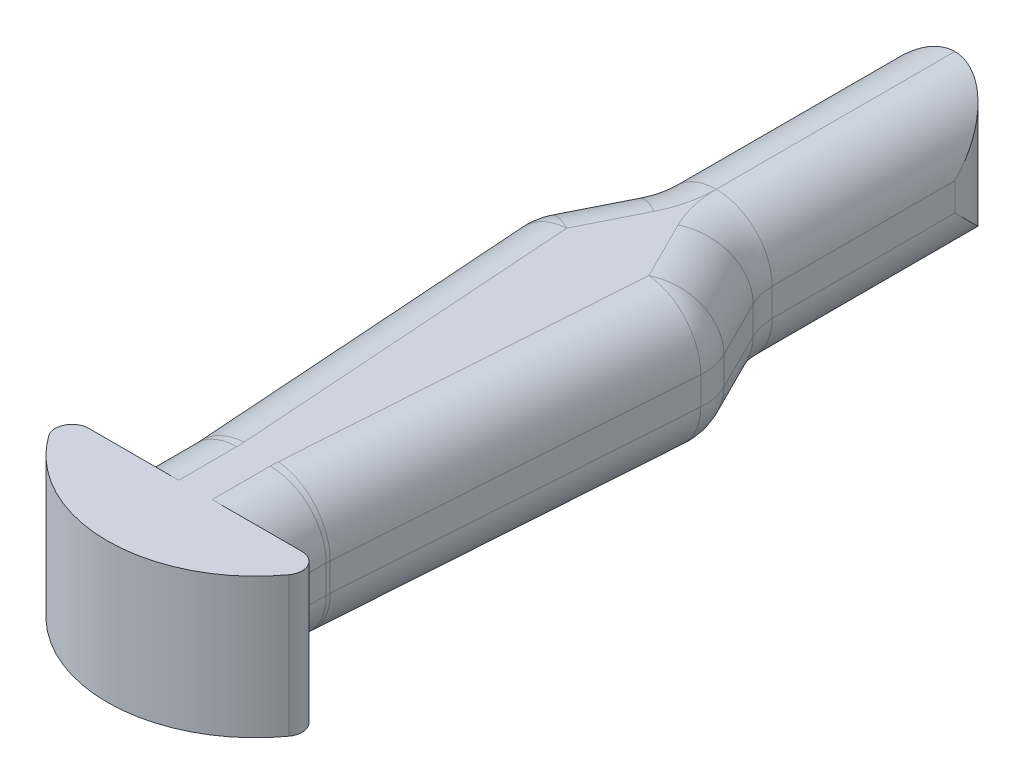
SolidWorks part; units mm, degrees
material "ABS"
ref_plane "Front Plane" through (0, 0, 0) normal (0, 0, 1) x (1, 0, 0)
ref_plane "Top Plane" through (0, 0, 0) normal (0, 1, 0) x (1, 0, 0)
ref_plane "Right Plane" through (0, 0, 0) normal (1, 0, 0) x (0, 0, -1)
sketch "草图1" plane through (0, 0, 0) normal (0, 1, 0) x (1, 0, 0)
  line L0 (0, 62.5) -> (0, -62.5)
  line L1 (-30, 62.5) -> (30, 62.5)
  line L2 (-30, 62.5) -> (-30, -62.5)
  line L3 (-30, -62.5) -> (30, -62.5)
  line L4 (30, 62.5) -> (30, -62.5)
  line L5 (-30, 62.5) -> (30, -62.5) construction
  line L6 (-30, -62.5) -> (30, 62.5) construction
  line L7 (-17.5, 2.5) -> (-10, 17.5)
  line L8 (0, -62.5) -> (13, -62.5)
  line L9 (0, -62.5) -> (0, 2.5)
  line L10 (0, 2.5) -> (13, 2.5)
  line L11 (13, -62.5) -> (13, 2.5)
  line L12 (0, -62.5) -> (-13, -62.5)
  line L13 (0, -62.5) -> (0, 2.5)
  line L14 (0, 2.5) -> (-13, 2.5)
  line L15 (-13, -62.5) -> (-13, 2.5)
  line L16 (30, 62.5) -> (10, 62.5)
  line L17 (30, 62.5) -> (30, 17.5)
  line L18 (30, 17.5) -> (10, 17.5)
  line L19 (10, 62.5) -> (10, 17.5)
  line L20 (-30, 62.5) -> (-10, 62.5)
  line L21 (-30, 62.5) -> (-30, 17.5)
  line L22 (-30, 17.5) -> (-10, 17.5)
  line L23 (-10, 62.5) -> (-10, 17.5)
  line L24 (0, -62.5) -> (17.5, -62.5)
  line L25 (0, -62.5) -> (0, 2.5)
  line L26 (0, 2.5) -> (17.5, 2.5)
  line L27 (17.5, -62.5) -> (17.5, 2.5)
  line L28 (0, -62.5) -> (-17.5, -62.5)
  line L29 (0, -62.5) -> (0, 2.5)
  line L30 (0, 2.5) -> (-17.5, 2.5)
  line L31 (-17.5, -62.5) -> (-17.5, 2.5)
  line L32 (10, 17.5) -> (17.5, 2.5)
  line L33 (-17.5, 2.5) -> (-13, -62.5)
  line L34 (17.5, 2.5) -> (13, -62.5)
  line L35 (-13, -62.5) -> (-13, -85.2565)
  line L36 (-13, -62.5) -> (13, -62.5)
  line L37 (-13, -62.5) -> (-13, -72.5)
  line L38 (-13, -72.5) -> (13, -72.5)
  line L39 (13, -62.5) -> (13, -72.5)
  line L40 (-13, -85.2565) -> (13, -85.2565)
  line L41 (13, -85.2565) -> (13, -62.5)
  line L42 (-13, -73.2227) -> (-24.2111, -73.2227)
  line L43 (-24.2111, -73.2227) -> (24.2111, -73.2227)
  arc A0 (-13, -73.2227) -> (13, -73.2227) centre (0, -62.5) ccw
  arc A1 (16.8516, -62.5) -> (-16.8516, -62.5) centre (0, -62.5) ccw
  arc A2 (26.4793, -62.5) -> (-26.4793, -62.5) centre (0, -62.5) ccw
  arc A3 (-24.2111, -73.2227) -> (24.2111, -73.2227) centre (0, -62.5) ccw
  point P0 (0, 0)
extrude "凸台-拉伸1" add sketch "草图1" along normal blind 25 contours L42 A3 L43 L41 L40 L35 | A0 L35 L40 L41 | L43 A0 | L35 L43 L41 L38 | L39 L3 L35 L38 | L29 A1 L15 L3 | L11 A1 L29 L3 | L11 A2 L29 A1 | L29 A2 L15 A1 | A2 L0 L14 L15 | A2 L11 L10 L0 | L30 L14 L0 L1 L23 L7 | L32 L19 L1 L0 L10 L26 | A2 L34 L26 L11 | A2 L15 L30 L33 | L34 A2 L11 A1 | L15 A2 L33 A1 | L34 A1 L11 | L15 A1 L33 region at (5.6429, 0, -30.3571) region at (-5.6429, 0, -30.3571) region at (6.5919, 0, 17.3261) region at (-6.5919, 0, 17.3261) region at (6.7568, 0, 42.4211) region at (-6.7568, 0, 42.4211) region at (14.6361, 0, 15.2775) region at (-14.6361, 0, 15.2775) region at (6.0789, 0, 54.9042) region at (-6.0789, 0, 54.9042) region at (13.5851, 0, 45.2827) region at (-13.5851, 0, 45.2827) region at (0, 0, 67.5) region at (13.2273, 0, 55.6397) region at (-13.2273, 0, 55.6397) region at (0, 0, 72.8614) region at (0, 0, 81.1715) region at (-13.5092, 0, 79.2396) region at (0, 0, 75.717)
fillet "圆角1" radius 3 2 edges at (24.2111, 12.5, 73.2227) (-24.2111, 12.5, 73.2227)
fillet "圆角2" radius 10 24 edges at (-13, 25, 67.8614) (-13, 0, 67.8614) (13, 25, 67.8614) (13, 0, 67.8614) (13.75, 25, -10) (13.75, 0, -10) (-10, 12.5, -62.5) (-10, 25, -40) (-10, 0, -40) (-10, 12.5, -17.5) (-13.75, 25, -10) (-13.75, 0, -10) (-17.5, 12.5, -2.5) (-15.25, 25, 30) (-13, 12.5, 62.5) (-15.25, 0, 30) (13, 12.5, 62.5) (15.25, 25, 30) (17.5, 12.5, -2.5) (15.25, 0, 30) (10, 12.5, -17.5) (10, 25, -40) (10, 12.5, -62.5) (10, 0, -40)
